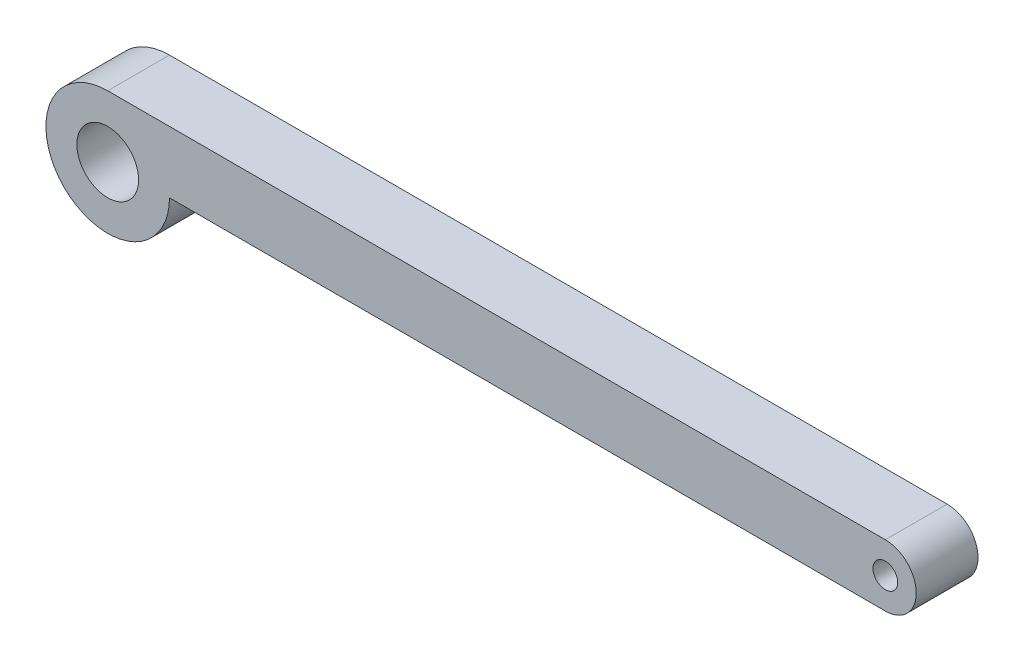
SolidWorks part; units mm, degrees
ref_plane "Front Plane" through (0, 0, 0) normal (1, 0, 0) x (0, 1, 0)
ref_plane "Top Plane" through (0, 0, 0) normal (0, 0, 1) x (0, 1, 0)
ref_plane "Right Plane" through (0, 0, 0) normal (0, 1, 0) x (-1, 0, 0)
sketch "Sketch1" plane through (0, 0, 0) normal (0, 0, 1) x (0, 1, 0)
  line L0 (10, 0) -> (10, -125.8887)
  line L1 (0, 0) -> (0, -125.8887) construction
  line L2 (0, -10) -> (0, -125.8887)
  circle A0 centre (0, 0) radius 10 construction
  circle A1 centre (5, -125.8887) radius 2
  arc A2 (0, -125.8887) -> (10, -125.8887) centre (5, -125.8887) ccw
  arc A4 (10, 0) -> (0, -10) centre (0, 0) ccw
  circle A5 centre (0, 0) radius 5
  dimension "D3" = 4
  dimension "D1" = 10
  dimension "D6" = 5
  dimension "D2" = 125.988
extrude "Boss-Extrude1" add sketch "Sketch1" along normal blind 10
equation "\"D3@Sketch1\" = \"BearingBore\""
equation "\"D1@Sketch1\"=\"BearingDiameter\""
equation "\"ThighLength\"= 200"
equation "\"BearingBore\"=4"
equation "\"MinShinWidth\"= 20"
equation "\"HipBore\"=27"
equation "\"ShinThickness\"=10"
equation "\"ThighThickness\"=30"
equation "\"MaxBending\"=135"
equation "\"MaxStretchingAngle\"= 140"
equation "\"ThighJointDistance\"=157.485"
equation "\"D2@Sketch1\"=\"ThighJointDistance\"*0.8"
equation "\"PivotDistance\"=50"
equation "\"ShinLength\"=100"
equation "\"BearingDiameter\"= 10"
